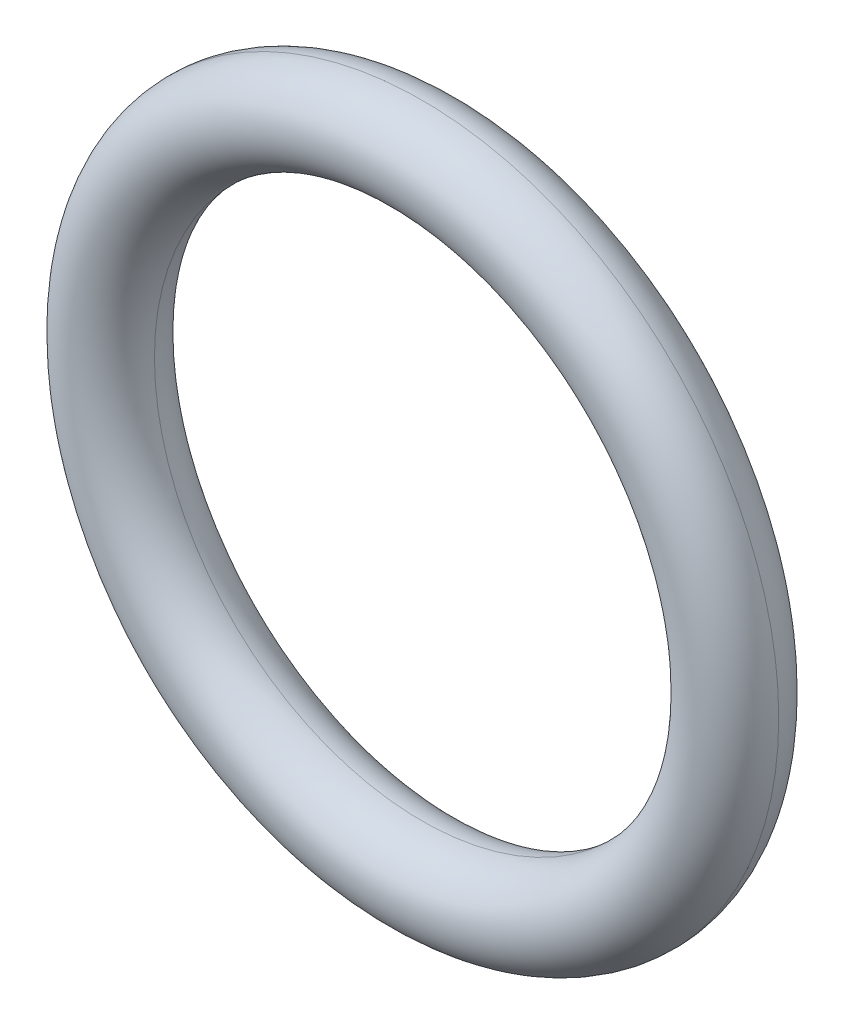
SolidWorks part; units mm, degrees
material "VITON"
ref_plane "Front" through (0, 0, 0) normal (0, 0, 1) x (1, 0, 0)
ref_plane "Top" through (0, 0, 0) normal (0, 1, 0) x (1, 0, 0)
ref_plane "Right" through (0, 0, 0) normal (1, 0, 0) x (0, 0, -1)
sketch "Sketch1" plane through (0, 0, 0) normal (0, 0, 1) x (1, 0, 0)
  circle A0 centre (0, 0) radius 4
extrude "Boss-Extrude1" add sketch "Sketch1" along normal blind 2
sketch "Sketch2" plane through (0, 0, 2) normal (0, 0, 1) x (1, 0, 0)
  circle A0 centre (0, 0) radius 3
extrude "Cut-Extrude1" cut sketch "Sketch2" against normal blind 2
fillet "Fillet3" radius 1 2 edges at (4, 0, 0) (4, 0, 2)
fillet "Fillet4" radius 0.5 2 edges at (3, 0, 2) (3, 0, 0)
